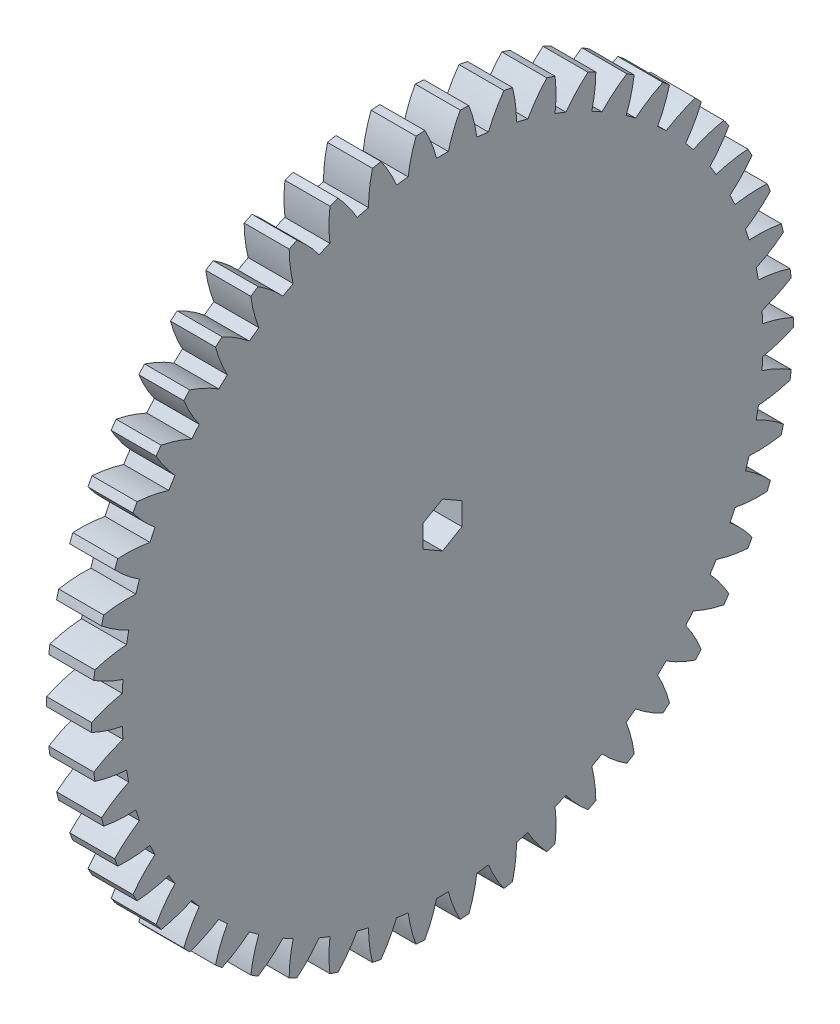
SolidWorks part; units mm, degrees
ref_plane "Plane1" through (0, 0, 0) normal (0, 0, 1) x (1, 0, 0)
ref_plane "Plane2" through (0, 0, 0) normal (0, 1, 0) x (1, 0, 0)
ref_plane "Plane3" through (0, 0, 0) normal (1, 0, 0) x (0, 0, -1)
sketch "HoldingSke" plane through (0, 0, 0) normal (0, 1, 0) x (1, 0, 0)
  line L0 (0, 0) -> (0.4285, -0.5107)
  line L1 (-15, 0) -> (100, 0) construction
  line L2 (0, 0) -> (-2.1039, 2.3779)
  line L3 (0, 0) -> (-11.863, 4.5341)
  line L4 (0, 0) -> (5.5511, 6.6156)
  line L5 (0, 0) -> (-46.8476, -17.4728)
  line L6 (0, 0) -> (-4.1448, -2.7965)
  line L7 (-2.1039, 2.3779) -> (8.6586, 51.2059)
  line L8 (-76.2, 54.61) -> (-75.3, 54.61)
  line L9 (-71.009, 38.7566) -> (-53.1078, 45.2721)
  line L10 (-76.2, 71.12) -> (104.1128, 71.12)
  line L11 (0, 0) -> (-5, 0)
  line L12 (-76.2, 101.6) -> (-76.147, 101.6)
  line L13 (24.9733, 27.94) -> (52.9518, 28.4284)
  line L14 (24.9733, 27.94) -> (24.9743, 27.94)
  line L15 (24.9733, 27.94) -> (100.4006, 29.5858)
  line L16 (-63.627, -1.5) -> (-12.827, -1.5)
  circle A0 centre (0, 0) radius 2.5
  circle A1 centre (0, 0) radius 35.624
  circle A2 centre (0, 0) radius 37.5
  circle A3 centre (0, 0) radius 2.5
  dimension "MHD" = 71.248
  dimension "Hub_dia" = 75
  dimension "Bore" = 5
  dimension "MBD" = 5
  dimension "Num_teeth" = 50
  dimension "Pitch" = 0.6667
  dimension "Overall_len" = 50
  dimension "Show_teeth" = 50
  dimension "Thickness" = 5
  dimension "OAL" = 50.0001
  dimension "T_dim" = 0.9
  dimension "Ap" = 20
  dimension "H" = 19.05
  dimension "Pitch_radius" = 180.3128
  dimension "Width" = 5
  dimension "Backlash" = 0.053
  dimension "Addendum_fac" = 1
  dimension "Dedendum_fac" = 1.25
  dimension "Clearance_fac" = 0.25
  dimension "Dedendum_add" = 0.001
  dimension "Module" = 1.5
sketch "BasProSke" plane through (0, 0, 0) normal (0, 1, 0) x (1, 0, 0)
  line L0 (-10, 0) -> (60, 0) construction
  line L1 (0, 0) -> (0, 39)
  line L2 (0, 0) -> (5, 0)
  line L3 (5, 0) -> (5, 39)
  line L4 (5, 39) -> (0, 39)
  dimension "Thickness" = 5
  dimension "Diameter" = 78
revolve "Base-Revolve" add sketch "BasProSke" angle 360 about L0
sketch "TooCutSke" plane through (0, 0, 0) normal (1, 0, 0) x (0, 0, -1)
  line L1 (0, 0) -> (0, 107) construction
  line L2 (0, 0) -> (-1.2706, 37.4785) construction
  line L3 (0, 0) -> (-4.7073, 74.8207) construction
  line L4 (-1.2706, 37.4785) -> (-2.3537, 37.4103) construction
  arc A0 (0.65, 35.6181) -> (-0.65, 35.6181) centre (0, 0) ccw
  arc A1 (1.9801, 38.9751) -> (-1.9801, 38.9751) centre (0, 0) ccw
  circle A2 centre (0, 0) radius 37.5 construction
  circle A3 centre (0, 0) radius 35.2385 construction
  arc A4 (-0.65, 35.6181) -> (-1.9801, 38.9751) centre (-15.1589, 31.8113) ccw
  arc A5 (1.9801, 38.9751) -> (0.65, 35.6181) centre (15.1589, 31.8113) ccw
  dimension "Root_dia" = 71.248
  dimension "Overcut_dia" = 78.0508
  dimension "Pitch_dia" = 75
  dimension "Base_dia" = 70.4769
  dimension "Flank_rad" = 15
  dimension "Half_ang" = 3.6
  dimension "Half_CT" = 1.0852
extrude "ToothCut" cut sketch "TooCutSke" along normal through all
fillet "Breaks" [suppressed] radius 0.03 tangent propagation no
fillet "RootFillets" [suppressed] radius 0.376
pattern_circular "TeethCuts" count 50 every 7.2 about axis through (-10, 0, 0) along (1, 0, 0) of "ToothCut", "RootFillets", "Breaks"
sketch "HubNeaOneSke" plane through (0, 0, 0) normal (-1, 0, 0) x (0, 0, 1)
  circle A0 centre (0, 0) radius 35.624
  dimension "Diameter" = 71.248
extrude "HubNearOne" [suppressed] add sketch "HubNeaOneSke" along normal blind 45.0001
sketch "HubNeaBotSke" plane through (0, 0, 0) normal (-1, 0, 0) x (0, 0, 1)
  circle A0 centre (0, 0) radius 35.624
  dimension "Diameter" = 71.248
extrude "HubNearBoth" [suppressed] add sketch "HubNeaBotSke" along normal blind 22.5
ref_plane "FarPln" through (5, 0, 0) normal (1, 0, 0) x (0, 0, -1)
sketch "HubFarSke" plane through (5, 0, 0) normal (1, 0, 0) x (0, 0, -1)
  circle A0 centre (0, 0) radius 35.624
  dimension "Diameter" = 71.248
extrude "HubFar" [suppressed] add sketch "HubFarSke" along normal blind 22.5
sketch "BorSke" plane through (0, 0, 0) normal (1, 0, 0) x (0, 0, -1)
  line L1 (0, -2.5) -> (2.1651, -1.25)
  line L2 (2.1651, -1.25) -> (2.1651, 1.25)
  line L3 (2.1651, 1.25) -> (0, 2.5)
  line L4 (0, 2.5) -> (-2.1651, 1.25)
  line L5 (-2.1651, 1.25) -> (-2.1651, -1.25)
  line L6 (-2.1651, -1.25) -> (0, -2.5)
  circle A0 centre (0, 0) radius 2.5 construction
  circle A1 centre (0, 0) radius 2.1651 construction
  point P2 (0, 0)
  point P11 (0, -2.5)
  dimension "Diameter" = 5
extrude "Bore" cut sketch "BorSke" along normal mid plane 100.0001
sketch "KeySke" plane through (0, 0, 0) normal (1, 0, 0) x (0, 0, -1)
  line L0 (-1, 0) -> (-1, 3.4)
  line L1 (-1, 3.4) -> (1, 3.4)
  line L2 (1, 3.4) -> (1, 0)
  line L3 (0, 0) -> (0, 34) construction
  line L4 (-1, 0) -> (1, 0)
  dimension "Offset" = 3.4
  dimension "Width" = 2
extrude "Keyway" [suppressed] cut sketch "KeySke" along normal mid plane 100.0001
pattern_circular "Keyway2" [suppressed] count 2 every 90 about axis through (-10, 0, 0) along (1, 0, 0) reverse direction yes
sketch "Sketch1" plane through (0, 0, 0) normal (-1, 0, 0) x (0, 0, 1)
  line L12 (2.1651, -1.25) -> (2.1651, 1.25) construction
  line L13 (2.1651, 1.25) -> (0, 2.5) construction
  line L14 (0, 2.5) -> (-2.1651, 1.25) construction
  line L15 (-2.1651, 1.25) -> (-2.1651, -1.25) construction
  line L16 (-2.1651, -1.25) -> (0, -2.5) construction
  line L17 (0, -2.5) -> (2.1651, -1.25) construction
  line L18 (2.1651, -1.25) -> (2.1651, 1.25)
  line L19 (2.1651, 1.25) -> (0, 2.5)
  line L20 (0, 2.5) -> (-2.1651, 1.25)
  line L21 (-2.1651, 1.25) -> (-2.1651, -1.25)
  line L22 (-2.1651, -1.25) -> (0, -2.5)
  line L23 (0, -2.5) -> (2.1651, -1.25)
  line L24 (4.5499, -3.3057) -> (-4.5499, 3.3057) construction
  arc A40 (0.1868, -8.9981) -> (0.8757, -5.5554) centre (-1.8542, -6.7994) ccw
  arc A41 (-0.1868, -8.9981) -> (0.1868, -8.9981) centre (0, 0) ccw
  arc A42 (-0.8757, -5.5554) -> (-0.1868, -8.9981) centre (1.8542, -6.7994) ccw
  arc A43 (-2.5569, -5.0091) -> (-0.8757, -5.5554) centre (0, 0) ccw
  arc A44 (-5.1378, -7.3894) -> (-2.5569, -5.0091) centre (-5.4967, -4.4109) ccw
  arc A45 (-5.4401, -7.1698) -> (-5.1378, -7.3894) centre (0, 0) ccw
  arc A46 (-3.9738, -3.9797) -> (-5.4401, -7.1698) centre (-2.4965, -6.5907) ccw
  arc A47 (-5.0129, -2.5496) -> (-3.9738, -3.9797) centre (0, 0) ccw
  arc A48 (-8.4999, -2.9582) -> (-5.0129, -2.5496) centre (-7.0396, -0.3377) ccw
  arc A49 (-8.6154, -2.6029) -> (-8.4999, -2.9582) centre (0, 0) ccw
  arc A50 (-5.5541, -0.8839) -> (-8.6154, -2.6029) centre (-5.8936, -3.8646) ccw
  arc A51 (-5.5541, 0.8839) -> (-5.5541, -0.8839) centre (0, 0) ccw
  arc A52 (-8.6154, 2.6029) -> (-5.5541, 0.8839) centre (-5.8936, 3.8646) ccw
  arc A53 (-8.4999, 2.9582) -> (-8.6154, 2.6029) centre (0, 0) ccw
  arc A54 (-5.0129, 2.5496) -> (-8.4999, 2.9582) centre (-7.0396, 0.3377) ccw
  arc A55 (-3.9738, 3.9797) -> (-5.0129, 2.5496) centre (0, 0) ccw
  arc A56 (-5.4401, 7.1698) -> (-3.9738, 3.9797) centre (-2.4965, 6.5907) ccw
  arc A57 (-5.1378, 7.3894) -> (-5.4401, 7.1698) centre (0, 0) ccw
  arc A58 (-2.5569, 5.0091) -> (-5.1378, 7.3894) centre (-5.4967, 4.4109) ccw
  arc A59 (-0.8757, 5.5554) -> (-2.5569, 5.0091) centre (0, 0) ccw
  arc A60 (-0.1868, 8.9981) -> (-0.8757, 5.5554) centre (1.8542, 6.7994) ccw
  arc A61 (0.1868, 8.9981) -> (-0.1868, 8.9981) centre (0, 0) ccw
  arc A62 (0.8757, 5.5554) -> (0.1868, 8.9981) centre (-1.8542, 6.7994) ccw
  arc A63 (2.5569, 5.0091) -> (0.8757, 5.5554) centre (0, 0) ccw
  arc A64 (5.1378, 7.3894) -> (2.5569, 5.0091) centre (5.4967, 4.4109) ccw
  arc A65 (5.4401, 7.1698) -> (5.1378, 7.3894) centre (0, 0) ccw
  arc A66 (3.9738, 3.9797) -> (5.4401, 7.1698) centre (2.4965, 6.5907) ccw
  arc A67 (5.0129, 2.5496) -> (3.9738, 3.9797) centre (0, 0) ccw
  arc A68 (8.4999, 2.9582) -> (5.0129, 2.5496) centre (7.0396, 0.3377) ccw
  arc A69 (8.6154, 2.6029) -> (8.4999, 2.9582) centre (0, 0) ccw
  arc A70 (5.5541, 0.8839) -> (8.6154, 2.6029) centre (5.8936, 3.8646) ccw
  arc A71 (5.5541, -0.8839) -> (5.5541, 0.8839) centre (0, 0) ccw
  arc A72 (8.6154, -2.6029) -> (5.5541, -0.8839) centre (5.8936, -3.8646) ccw
  arc A73 (8.4999, -2.9582) -> (8.6154, -2.6029) centre (0, 0) ccw
  arc A74 (5.0129, -2.5496) -> (8.4999, -2.9582) centre (7.0396, -0.3377) ccw
  arc A75 (3.9738, -3.9797) -> (5.0129, -2.5496) centre (0, 0) ccw
  arc A76 (5.4401, -7.1698) -> (3.9738, -3.9797) centre (2.4965, -6.5907) ccw
  arc A77 (5.1378, -7.3894) -> (5.4401, -7.1698) centre (0, 0) ccw
  arc A78 (2.5569, -5.0091) -> (5.1378, -7.3894) centre (5.4967, -4.4109) ccw
  arc A79 (0.8757, -5.5554) -> (2.5569, -5.0091) centre (0, 0) ccw
  point P21 (0, 0)
extrude "Boss-Extrude1" add sketch "Sketch1" along normal blind 6
equation "' \"Module@HoldingSke\" = 6.35"
equation "' \"Num_teeth@HoldingSke\" = 12"
equation "' \"Ap@HoldingSke\" =  20"
equation "' \"Ap@HoldingSke\" = 20"
equation "' \"Width@HoldingSke\" = 0.5 * 25.4"
equation "' \"Hub_dia@HoldingSke\"= 1 * 25.4"
equation "' \"Hub_dia@HoldingSke\" = 1 * 25.4"
equation "' \"Overall_len@HoldingSke\" = 1.0 * 25.4"
equation "' \"Bore@HoldingSke\" = 0.75 * 25.4"
equation "' \"T_dim@HoldingSke\" = 0.1 * 25.4"
equation "' \"Width@KeySke\" = 0.25 * 25.4"
equation "' \"Show_teeth@HoldingSke\" = 13"
equation "' \"Backlash@HoldingSke\" = 0.009 * 25.4"
equation "' \"Addendum_fac@HoldingSke\" = 1.0"
equation "' \"Dedendum_fac@HoldingSke\" = 1.25"
equation "' \"Dedendum_add@HoldingSke\" = 0.00005 * 25.4"
equation "' \"Clearance_fac@HoldingSke\" = 0.25"
equation "\"Pitch@HoldingSke\" = 1 / \"Module@HoldingSke\""
equation "\"Overcut_dia@TooCutSke\" = (\"Num_teeth@HoldingSke\" + 2 * \"Addendum_fac@HoldingSke\") / \"Pitch@HoldingSke\" + 0.002 * 25.4"
equation "\"Pitch_dia@TooCutSke\" = \"Num_teeth@HoldingSke\" / \"Pitch@HoldingSke\""
equation "\"Base_dia@TooCutSke\" = \"Num_teeth@HoldingSke\" / \"Pitch@HoldingSke\" * cos((\"Ap@HoldingSke\"  * 3.14159265 / 180))"
equation "\"Root_dia@TooCutSke\" = (\"Num_teeth@HoldingSke\" + 2) / \"Pitch@HoldingSke\" - 2 * (\"Addendum_fac@HoldingSke\" + \"Dedendum_fac@HoldingSke\") / \"Pitch@HoldingSke\" - \"Dedendum_add@HoldingSke\" * 2"
equation "\"Half_ang@TooCutSke\" = 180 / \"Num_teeth@HoldingSke\""
equation "\"Half_CT@TooCutSke\" = \"Num_teeth@HoldingSke\" / \"Pitch@HoldingSke\" * sin((3.14159265 / 2 / \"Num_teeth@HoldingSke\")) / 2 - 7 * \"Backlash@HoldingSke\" / 4"
equation "\"Flank_rad@TooCutSke\" = \"Num_teeth@HoldingSke\" / \"Pitch@HoldingSke\" / 5"
equation "\"Radius@RootFillets\" = \"Clearance_fac@HoldingSke\" / \"Pitch@HoldingSke\" + \"Dedendum_add@HoldingSke\""
equation "\"Break_rad@Breaks\" = 0.02 / \"Pitch@HoldingSke\""
equation "\"Thickness@HoldingSke\" = \"Width@HoldingSke\""
equation "\"OAL@HoldingSke\" = \"Thickness@HoldingSke\""
equation "\"MHD@HoldingSke\" = (\"Num_teeth@HoldingSke\" + 2) / \"Pitch@HoldingSke\" - 2 * (\"Addendum_fac@HoldingSke\" + \"Dedendum_fac@HoldingSke\")  / \"Pitch@HoldingSke\" - \"Dedendum_add@HoldingSke\" * 2"
equation "\"MBD@HoldingSke\" = (\"Num_teeth@HoldingSke\" + 2) / \"Pitch@HoldingSke\" - 2 * (\"Addendum_fac@HoldingSke\" + \"Dedendum_fac@HoldingSke\")  / \"Pitch@HoldingSke\" - \"Dedendum_add@HoldingSke\" * 2 - 0.002 * 25.4"
equation "\"MHD@HoldingSke\" = ((sgn( \"MHD@HoldingSke\" - \"Hub_dia@HoldingSke\" )-1)*( \"MHD@HoldingSke\" - \"Hub_dia@HoldingSke\" ))/-2+ \"Hub_dia@HoldingSke\""
equation "\"MBD@HoldingSke\" = ((sgn( \"MBD@HoldingSke\" - \"Bore@HoldingSke\" )-1)*( \"MBD@HoldingSke\" - \"Bore@HoldingSke\" ))/-2+ \"Bore@HoldingSke\""
equation "\"OAL@HoldingSke\" = ((sgn( \"OAL@HoldingSke\" - \"Overall_len@HoldingSke\" )+1)*( \"OAL@HoldingSke\" - \"Overall_len@HoldingSke\" ))/2 + \"Overall_len@HoldingSke\" + 0.000002 * 25.4"
equation "\"Num_teeth@TeethCuts\" = int( \"Show_teeth@HoldingSke\" ) + 1"
equation "\"Num_teeth@TeethCuts\" = ((sgn( \"Num_teeth@TeethCuts\" - \"Num_teeth@HoldingSke\" )-1)*( \"Num_teeth@TeethCuts\" - \"Num_teeth@HoldingSke\" ))/-2+ \"Num_teeth@HoldingSke\""
equation "\"Num_teeth@TeethCuts\" = ((sgn( \"Num_teeth@TeethCuts\" - 2.0)+1)*( \"Num_teeth@TeethCuts\" - 2.0))/2 +2.0"
equation "\"Angle@TeethCuts\" = 360.0 / \"Num_teeth@HoldingSke\""
equation "\"Diameter@BasProSke\" = (\"Num_teeth@HoldingSke\" + 2 * \"Addendum_fac@HoldingSke\") / \"Pitch@HoldingSke\""
equation "\"Thickness@BasProSke\"  = \"Thickness@HoldingSke\""
equation "' \"Fillet_rad@BasProSke\" =  \"Thickness@HoldingSke\" * 0.05"
equation "' \"Fillet_rad@BasProSke\" = \"Thickness@HoldingSke\" * 0.05"
equation "\"MHD@HoldingSke\" = ((sgn( \"MHD@HoldingSke\" - \"Root_dia@TooCutSke\" )-1)*( \"MHD@HoldingSke\" - \"Root_dia@TooCutSke\" ))/-2+ \"Root_dia@TooCutSke\""
equation "\"Diameter@HubNeaOneSke\" = \"MHD@HoldingSke\""
equation "\"Length@HubNearOne\" = \"OAL@HoldingSke\" - \"Thickness@BasProSke\""
equation "\"Diameter@HubNeaBotSke\" = \"MHD@HoldingSke\""
equation "\"Length@HubNearBoth\" = ( \"OAL@HoldingSke\" - \"Thickness@BasProSke\" ) / 2.0"
equation "\"Thickness@FarPln\" = \"Thickness@BasProSke\""
equation "\"Diameter@HubFarSke\" = \"MHD@HoldingSke\""
equation "\"Length@HubFar\" = ( \"OAL@HoldingSke\" - \"Thickness@BasProSke\" ) / 2.0"
equation "\"Diameter@BorSke\" = \"MBD@HoldingSke\""
equation "\"D1@Bore\" = \"OAL@HoldingSke\" * 2.0"
equation "\"D1@Keyway\" = \"OAL@HoldingSke\" * 2.0"
equation "\"Offset@KeySke\" = \"T_dim@HoldingSke\" + \"MBD@HoldingSke\" / 2.0"
